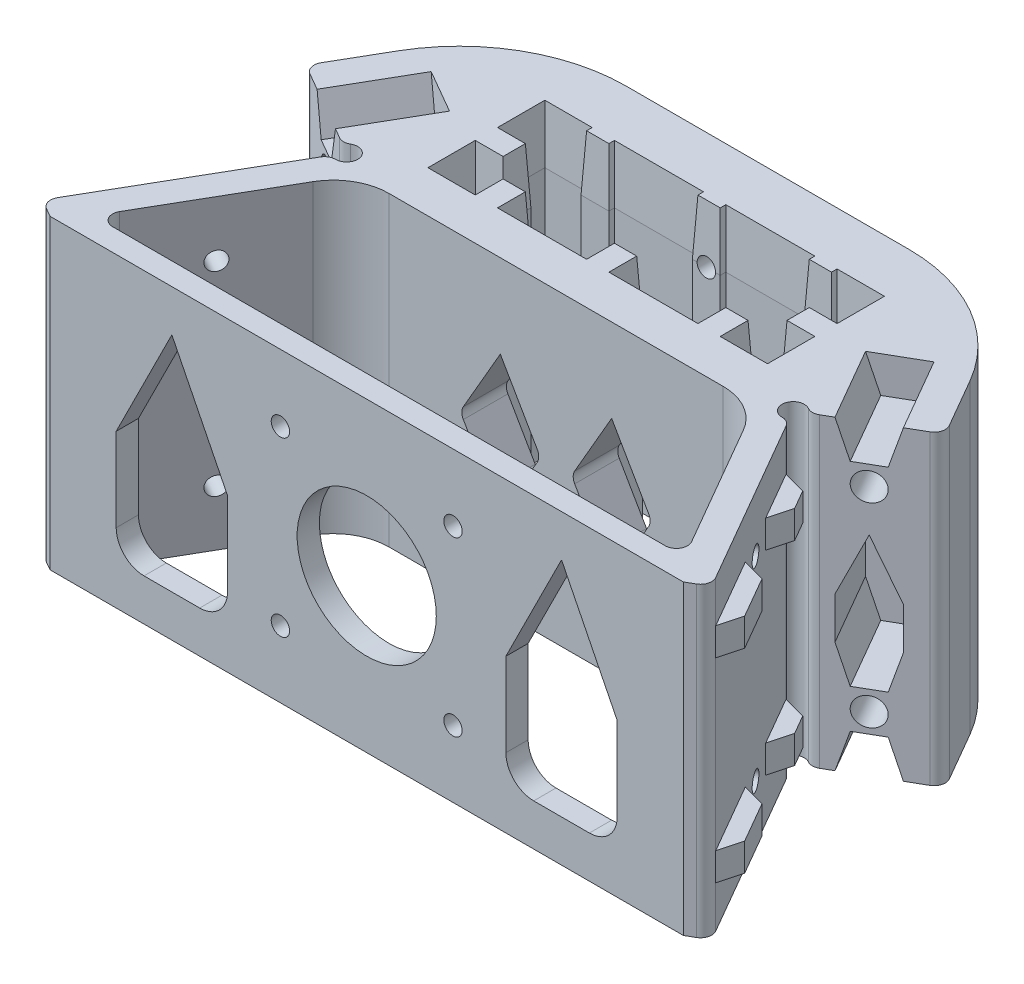
SolidWorks part; units mm, degrees
ref_plane "Front Plane" through (0, 0, 0) normal (0, 0, 1) x (1, 0, 0)
ref_plane "Top Plane" through (0, 0, 0) normal (0, 1, 0) x (1, 0, 0)
ref_plane "Right Plane" through (0, 0, 0) normal (1, 0, 0) x (0, 0, -1)
sketch "Sketch1" plane through (0, 0, 0) normal (0, 1, 0) x (1, 0, 0)
  line L0 (-30, -18) -> (30, -18)
  line L1 (-30, 10) -> (-22.5, 10)
  line L2 (-46.46, 5.4904) -> (-53.96, -7.5) construction
  line L3 (-30, -10) -> (-22.5, -10)
  line L4 (30, 10) -> (30, 2.5)
  line L5 (0, 0) -> (0, -75.5561) construction
  line L6 (38.6603, -23) -> (51.362, -45)
  line L7 (55.7735, -52.641) -> (58.3716, -51.141)
  line L8 (59.1036, -48.409) -> (41.8357, -18.5)
  line L9 (43.1036, -13.7679) -> (55.6921, -6.5)
  line L10 (56.4241, -3.7679) -> (51.362, 5)
  line L11 (25.3812, 20) -> (-25.3812, 20)
  line L12 (43.5677, -13.5) -> (36.0677, -0.5096) construction
  line L13 (36.0677, -0.5096) -> (46.46, 5.4904) construction
  line L14 (46.46, 5.4904) -> (53.96, -7.5) construction
  line L15 (-36.0677, -0.5096) -> (-46.46, 5.4904) construction
  line L16 (-43.5677, -13.5) -> (-36.0677, -0.5096) construction
  line L17 (-56.4241, -3.7679) -> (-51.362, 5)
  line L18 (-43.1036, -13.7679) -> (-55.6921, -6.5)
  line L19 (-59.1036, -48.409) -> (-41.8357, -18.5)
  line L20 (-55.7735, -52.641) -> (-58.3716, -51.141)
  line L21 (-38.6603, -23) -> (-51.362, -45)
  line L22 (-30, 10) -> (-30, 2.5)
  line L23 (30, 2.5) -> (25, 2.5)
  line L24 (25, 2.5) -> (25, -2.5)
  line L25 (25, -2.5) -> (30, -2.5)
  line L26 (30, -2.5) -> (30, -10)
  line L27 (22.5, -10) -> (22.5, -5)
  line L28 (22.5, -5) -> (17.5, -5)
  line L29 (17.5, -5) -> (17.5, -10)
  line L30 (22.5, -10) -> (30, -10)
  line L31 (17.5, 10) -> (17.5, 9)
  line L32 (17.5, 9) -> (22.5, 9)
  line L33 (22.5, 9) -> (22.5, 10)
  line L34 (22.5, 10) -> (30, 10)
  line L35 (2.5, -10) -> (2.5, -5)
  line L36 (2.5, -5) -> (-2.5, -5)
  line L37 (-2.5, -5) -> (-2.5, -10)
  line L38 (-2.5, 10) -> (-2.5, 9)
  line L39 (-2.5, 9) -> (2.5, 9)
  line L40 (2.5, 9) -> (2.5, 10)
  line L41 (-17.5, -10) -> (-17.5, -5)
  line L42 (-17.5, -5) -> (-22.5, -5)
  line L43 (-22.5, -5) -> (-22.5, -10)
  line L44 (-22.5, 10) -> (-22.5, 9)
  line L45 (-22.5, 9) -> (-17.5, 9)
  line L46 (-17.5, 9) -> (-17.5, 10)
  line L47 (-17.5, 10) -> (-2.5, 10)
  line L48 (-17.5, -10) -> (-2.5, -10)
  line L49 (2.5, -10) -> (17.5, -10)
  line L50 (2.5, 10) -> (17.5, 10)
  line L51 (-25, -2.5) -> (-30, -2.5)
  line L52 (-25, 2.5) -> (-25, -2.5)
  line L53 (-30, 2.5) -> (-25, 2.5)
  line L54 (-30, -2.5) -> (-30, -10)
  line L55 (-54.8261, -52) -> (54.8261, -52)
  line L56 (-49.6299, -48) -> (49.6299, -48)
  line L57 (-55.6921, -52.5) -> (-55.7735, -52.641)
  line L58 (55.6921, -52.5) -> (55.7735, -52.641)
  circle A0 centre (0, 0) radius 31.6228 construction
  arc A1 (30, -18) -> (38.6603, -23) centre (30, -28) cw
  arc A2 (51.362, 5) -> (25.3812, 20) centre (25.3812, -10) ccw
  arc A3 (41.1036, -13.7679) -> (40.1036, -17.5) centre (40.1036, -15.5) ccw
  arc A4 (58.3716, -51.141) -> (59.1036, -48.409) centre (57.3716, -49.409) ccw
  arc A5 (55.6921, -6.5) -> (56.4241, -3.7679) centre (54.6921, -4.7679) ccw
  arc A6 (40.1036, -17.5) -> (41.8357, -18.5) centre (40.1036, -19.5) cw
  arc A7 (41.1036, -13.7679) -> (43.1036, -13.7679) centre (42.1036, -12.0359) ccw
  arc A8 (-41.1036, -13.7679) -> (-43.1036, -13.7679) centre (-42.1036, -12.0359) cw
  arc A9 (-40.1036, -17.5) -> (-41.8357, -18.5) centre (-40.1036, -19.5) ccw
  arc A10 (-55.6921, -6.5) -> (-56.4241, -3.7679) centre (-54.6921, -4.7679) cw
  arc A11 (-58.3716, -51.141) -> (-59.1036, -48.409) centre (-57.3716, -49.409) cw
  arc A12 (-41.1036, -13.7679) -> (-40.1036, -17.5) centre (-40.1036, -15.5) cw
  arc A13 (-51.362, 5) -> (-25.3812, 20) centre (-25.3812, -10) cw
  arc A14 (-30, -18) -> (-38.6603, -23) centre (-30, -28) ccw
  arc A15 (55.6921, -52.5) -> (54.8261, -52) centre (54.8261, -53) ccw
  arc A16 (-54.8261, -52) -> (-55.6921, -52.5) centre (-54.8261, -53) ccw
  arc A17 (49.6299, -48) -> (51.362, -45) centre (49.6299, -46) ccw
  arc A18 (-49.6299, -48) -> (-51.362, -45) centre (-49.6299, -46) cw
  point P7 (-57.4241, -5.5)
  point P9 (0, -18)
  point P22 (35.7735, -18)
  point P27 (0, 10)
  point P30 (60.1036, -50.141)
  point P33 (57.4241, -5.5)
  point P61 (0, 20)
  point P65 (-60.1036, -50.141)
  point P66 (-35.7735, -18)
  point P104 (55.4034, -52)
  point P107 (-55.4034, -52)
  dimension "D12" = 10
  dimension "D14" = 30
  dimension "D16" = 2
  dimension "D17" = 2
  dimension "D28" = 1
  dimension "D29" = 2
  dimension "D2" = 30
  dimension "D3" = 5
  dimension "D4" = 8
  dimension "D5" = 40
  dimension "D6" = 20
  dimension "D7" = 30
  dimension "D8" = 10
  dimension "D9" = 4
  dimension "D10" = 12
  dimension "D11" = 15
  dimension "D13" = 20
  dimension "D15" = 34
  dimension "D18" = 5
  dimension "D19" = 2.5
  dimension "D20" = 5
  dimension "D21" = 5
  dimension "D22" = 5
  dimension "D23" = 7.5
  dimension "D24" = 1
  dimension "D26" = 20
  dimension "D27" = 4
  dimension "D25" = 3
extrude "Boss-Extrude1" add sketch "Sketch1" along normal blind 55
sketch "Sketch13" plane through (16.7376, 0, 28.9904) normal (0.5, 0, 0.866) x (0.866, 0, -0.5)
  line L0 (30.4449, 0) -> (44.9808, 0) construction
  line L1 (26.9808, 55) -> (26.9808, 0) construction
  line L2 (30.4449, 55) -> (44.9808, 55) construction
  circle A0 centre (36.9808, 10) radius 5
  circle A1 centre (36.9808, 45) radius 5
  dimension "D2" = 10
  dimension "D1" = 10
  dimension "D3" = 10
  dimension "D5" = 10
  dimension "D4" = 2
extrude "Cut-Extrude7" cut sketch "Sketch13" against normal through all
sketch "Sketch14" plane through (16.7376, 0, 28.9904) normal (0.5, 0, 0.866) x (0.866, 0, -0.5)
  circle A0 centre (36.9808, 45) radius 5
  circle A1 centre (36.9808, 10) radius 5
  circle A2 centre (36.9808, 45) radius 5 construction
  circle A3 centre (36.9808, 10) radius 5 construction
  circle A4 centre (36.9808, 45) radius 2.5
  circle A5 centre (36.9808, 10) radius 2.5
  dimension "D1" = 5
  dimension "D2" = 5
extrude "Boss-Extrude8" add sketch "Sketch14" against normal blind 16
sketch "Sketch15" plane through (16.7376, 0, 28.9904) normal (0.5, 0, 0.866) x (0.866, 0, -0.5)
  line L0 (32.4808, 55) -> (34.4808, 48.5)
  line L1 (24.9808, 27.5) -> (44.9808, 27.5) construction
  line L2 (30.4449, 55) -> (44.9808, 55) construction
  line L3 (34.4808, 48.5) -> (39.4808, 48.5)
  line L4 (39.4808, 48.5) -> (41.4808, 55)
  line L5 (41.4808, 55) -> (32.4808, 55)
  line L6 (36.9808, 48.5) -> (36.9808, 55) construction
  line L7 (26.9808, 55) -> (26.9808, 0) construction
  line L8 (24.9808, 55) -> (24.9808, 0) construction
  line L9 (44.9808, 55) -> (44.9808, 0) construction
  line L10 (39.4808, 6.5) -> (41.4808, 0)
  line L11 (34.4808, 6.5) -> (39.4808, 6.5)
  line L12 (32.4808, 0) -> (34.4808, 6.5)
  line L13 (41.4808, 0) -> (32.4808, 0)
  line L14 (28.7128, 10) -> (36.9808, 10) construction
  line L15 (28.7128, 55) -> (28.7128, 0) construction
  line L16 (41.4808, 20) -> (41.4808, 27.5)
  line L17 (32.4808, 20) -> (34.4808, 13.5)
  line L18 (34.4808, 13.5) -> (39.4808, 13.5)
  line L19 (39.4808, 13.5) -> (41.4808, 20)
  line L20 (41.4808, 27.5) -> (36.9808, 37.5)
  line L21 (36.9808, 37.5) -> (32.4808, 27.5)
  line L22 (32.4808, 27.5) -> (32.4808, 20)
  dimension "D1" = 9
  dimension "D2" = 5
  dimension "D3" = 10
  dimension "D4" = 6.5
  dimension "D5" = 10
extrude "Cut-Extrude8" cut sketch "Sketch15" against normal blind 15
sketch "Sketch16" plane through (23.366, 0, -13.4904) normal (0.866, 0, -0.5) x (-0.5, 0, -0.866)
  line L0 (-71.4752, 55) -> (-71.4752, 0) construction
  line L1 (-71.4752, 7.5) -> (-56.9393, 7.5)
  line L2 (-71.4752, 7.5) -> (-71.4752, 12.5)
  line L3 (-71.4752, 12.5) -> (-56.9393, 12.5)
  line L4 (-36.9393, 7.5) -> (-36.9393, 12.5)
  line L5 (-36.9393, 55) -> (-36.9393, 0) construction
  line L6 (-71.4752, 0) -> (-36.9393, 0) construction
  line L7 (-71.4752, 47.5) -> (-56.9393, 47.5)
  line L8 (-71.4752, 47.5) -> (-71.4752, 42.5)
  line L9 (-71.4752, 42.5) -> (-56.9393, 42.5)
  line L10 (-36.9393, 47.5) -> (-36.9393, 42.5)
  line L11 (-71.4752, 55) -> (-36.9393, 55) construction
  line L12 (-56.9393, 47.5) -> (-56.9393, 42.5)
  line L13 (-46.9393, 7.5) -> (-46.9393, 12.5)
  line L14 (-46.9393, 47.5) -> (-36.9393, 47.5)
  line L15 (-46.9393, 42.5) -> (-36.9393, 42.5)
  line L16 (-46.9393, 12.5) -> (-36.9393, 12.5)
  line L17 (-46.9393, 7.5) -> (-36.9393, 7.5)
  line L18 (-46.9393, 42.5) -> (-46.9393, 47.5)
  line L19 (-56.9393, 12.5) -> (-56.9393, 7.5)
  dimension "D1" = 5
  dimension "D2" = 5
  dimension "D3" = 7.5
  dimension "D4" = 7.5
  dimension "D5" = 10
  dimension "D6" = 10
extrude "Boss-Extrude9" add sketch "Sketch16" along normal blind 3
chamfer "Chamfer2" distance 3 angle 45 8 edges at (44.4338, 45, 17) (44.4338, 10, 17) (49.4338, 10, 25.6603) (49.4338, 45, 25.6603) (54.4338, 45, 34.3205) (54.4338, 10, 34.3205) (61.7017, 10, 46.909) (61.7017, 45, 46.909)
sketch "Sketch17" plane through (23.366, 0, -13.4904) normal (0.866, 0, -0.5) x (-0.5, 0, -0.866)
  line L0 (-56.9393, 45) -> (-46.9393, 45) construction
  line L1 (-56.9393, 42.5) -> (-56.9393, 47.5) construction
  line L2 (-46.9393, 47.5) -> (-46.9393, 42.5) construction
  line L3 (-51.9393, 45) -> (-51.9393, 10) construction
  line L4 (-56.9393, 10) -> (-46.9393, 10) construction
  line L5 (-56.9393, 7.5) -> (-56.9393, 12.5) construction
  line L6 (-46.9393, 12.5) -> (-46.9393, 7.5) construction
  circle A0 centre (-51.9393, 10) radius 1.65
  circle A1 centre (-51.9393, 45) radius 1.65
  dimension "D1" = 3.3
  dimension "D2" = 2
extrude "Cut-Extrude9" cut sketch "Sketch17" against normal up to next
mirror "Mirror7" about plane through (0, 0, 0) normal (1, 0, 0) of "Cut-Extrude9", "Chamfer2", "Boss-Extrude9", "Cut-Extrude8", "Boss-Extrude8", "Cut-Extrude7"
sketch "Sketch18" plane through (0, 0, -20) normal (0, 0, -1) x (-1, 0, 0)
  line L0 (-25.3812, 27.5) -> (25.3812, 27.5) construction
  line L1 (-25.3812, 45) -> (-25.3812, 10) construction
  line L2 (25.3812, 45) -> (25.3812, 10) construction
  line L3 (0, 0) -> (0, 55) construction
  line L4 (-25.3812, 55) -> (25.3812, 55) construction
  line L5 (-25.3812, 0) -> (25.3812, 0) construction
  circle A0 centre (0, 45) radius 1.65
  circle A1 centre (0, 10) radius 1.65
  circle A2 centre (-20, 27.5) radius 1.65
  circle A3 centre (20, 27.5) radius 1.65
  dimension "D1" = 3.3
  dimension "D2" = 3.3
  dimension "D3" = 3.3
  dimension "D4" = 3.3
  dimension "D6" = 10
  dimension "D8" = 20
  dimension "D5" = 10
  dimension "D7" = 20
extrude "Cut-Extrude10" cut sketch "Sketch18" against normal up to next
sketch "Sketch19" plane through (0, 0, -20) normal (0, 0, -1) x (-1, 0, 0)
  circle A0 centre (0, 45) radius 6
  circle A1 centre (20, 27.5) radius 6
  circle A2 centre (0, 10) radius 6
  circle A3 centre (-20, 27.5) radius 6
  dimension "D1" = 12
  dimension "D2" = 12
  dimension "D3" = 12
  dimension "D4" = 12
extrude "Cut-Extrude11" cut sketch "Sketch19" against normal offset from surface (4 mm away) 7 up to face at (1.65, 10, -9)
sketch "Sketch20" plane through (0, 0, 18) normal (0, 0, 1) x (1, 0, 0)
  line L0 (-10, 40) -> (-16.6395, 28.5)
  line L1 (-16.6395, 26.5) -> (-11.7321, 18)
  line L2 (-8.2679, 18) -> (-3.3605, 26.5)
  line L3 (-3.3605, 28.5) -> (-10, 40)
  line L4 (-17.2169, 27.5) -> (-30, 27.5) construction
  line L5 (-30, 55) -> (-30, 0) construction
  line L6 (0, 0) -> (0, 55) construction
  line L7 (-30, 55) -> (30, 55) construction
  line L8 (3.3605, 28.5) -> (10, 40)
  line L9 (8.2679, 18) -> (3.3605, 26.5)
  line L10 (16.6395, 26.5) -> (11.7321, 18)
  line L11 (10, 40) -> (16.6395, 28.5)
  arc A0 (-3.3605, 26.5) -> (-3.3605, 28.5) centre (-5.0925, 27.5) ccw
  arc A1 (-16.6395, 28.5) -> (-16.6395, 26.5) centre (-14.9075, 27.5) ccw
  arc A2 (-11.7321, 18) -> (-8.2679, 18) centre (-10, 19) ccw
  arc A3 (11.7321, 18) -> (8.2679, 18) centre (10, 19) cw
  arc A4 (16.6395, 28.5) -> (16.6395, 26.5) centre (14.9075, 27.5) cw
  arc A5 (3.3605, 26.5) -> (3.3605, 28.5) centre (5.0925, 27.5) cw
  point P10 (-2.7831, 27.5)
  point P16 (-10, 15)
  point P31 (10, 15)
  point P32 (2.7831, 27.5)
  dimension "D6" = 2
  dimension "D1" = 60
  dimension "D2" = 60
  dimension "D3" = 120
  dimension "D4" = 25
  dimension "D5" = 10
extrude "Cut-Extrude12" cut sketch "Sketch20" against normal up to next
sketch "Sketch21" plane through (0, 0, 0) normal (0, 1, 0) x (1, 0, 0)
  line L0 (-30, -18) -> (30, -18) construction
  circle A0 centre (0, -18) radius 80
  dimension "D1" = 160
sketch "Sketch22" plane through (0, 55, 0) normal (0, 1, 0) x (1, 0, 0)
  line L0 (-54.8261, -52) -> (54.8261, -52) construction
  line L1 (-56.8838, -52) -> (56.8838, -52)
  line L2 (-56.8838, -52) -> (-56.8838, -52.641)
  line L3 (-56.8838, -52.641) -> (56.8838, -52.641)
  line L4 (56.8838, -52) -> (56.8838, -52.641)
  line L5 (-58.3716, -51.141) -> (-55.7735, -52.641) construction
  line L6 (55.7735, -52.641) -> (58.3716, -51.141) construction
extrude "Cut-Extrude13" cut sketch "Sketch22" against normal through all
sketch "Sketch23" plane through (0, 0, 52) normal (0, 0, 1) x (1, 0, 0)
  line L0 (0, 0) -> (0, 27.5) construction
  line L1 (0, 27.5) -> (56.8838, 27.5) construction
  line L2 (56.8838, 0) -> (56.8838, 55) construction
  line L3 (35, 7.5) -> (35, 47.5) construction
  line L4 (35, 47.5) -> (45, 27.5)
  line L5 (45, 27.5) -> (45, 7.5)
  line L6 (45, 7.5) -> (25, 7.5)
  line L7 (25, 27.5) -> (35, 47.5)
  line L8 (25, 7.5) -> (25, 27.5)
  line L9 (-45, 27.5) -> (-45, 7.5)
  line L10 (-45, 7.5) -> (-25, 7.5)
  line L11 (-25, 7.5) -> (-25, 27.5)
  line L12 (-35, 47.5) -> (-45, 27.5)
  line L13 (-25, 27.5) -> (-35, 47.5)
  circle A0 centre (0, 27.5) radius 12.5
  circle A1 centre (-15.5, 12) radius 1.65
  circle A2 centre (15.5, 12) radius 1.65
  circle A3 centre (15.5, 43) radius 1.65
  circle A4 centre (-15.5, 43) radius 1.65
  dimension "D1" = 25
  dimension "D2" = 3.3
  dimension "D4" = 15.5
  dimension "D8" = 31
  dimension "D3" = 15.5
  dimension "D7" = 31
  dimension "D9" = 20
  dimension "D10" = 20
  dimension "D11" = 40
  dimension "D12" = 35
  dimension "D5" = 2
  dimension "D6" = 2
extrude "Cut-Extrude14" cut sketch "Sketch23" against normal up to next
fillet "Fillet1" radius 5 4 edges at (45, 7.5, 50) (25, 7.5, 50) (-25, 7.5, 50) (-45, 7.5, 50)
chamfer "Chamfer3" distance 0.5 distance2 10 36 edges at (-30, 55, -6.25) (-27.5, 55, -2.5) (-25, 55, 0) (-27.5, 55, 2.5) (-30, 55, 6.25) (-26.25, 55, 10) (-22.5, 55, 7.5) (-20, 55, 5) (-17.5, 55, 7.5) (-10, 55, 10) (-2.5, 55, 7.5) (0, 55, 5) (2.5, 55, 7.5) (10, 55, 10) (17.5, 55, 7.5) (20, 55, 5) (22.5, 55, 7.5) (26.25, 55, 10) (30, 55, 6.25) (27.5, 55, 2.5) (25, 55, 0) (27.5, 55, -2.5) (30, 55, -6.25) (26.25, 55, -10) (22.5, 55, -9.5) (20, 55, -9) (17.5, 55, -9.5) (10, 55, -10) (2.5, 55, -9.5) (0, 55, -9) (-2.5, 55, -9.5) (-10, 55, -10) (-17.5, 55, -9.5) (-20, 55, -9) (-22.5, 55, -9.5) (-26.25, 55, -10) first distance on face at (0, 55, 14.172)
